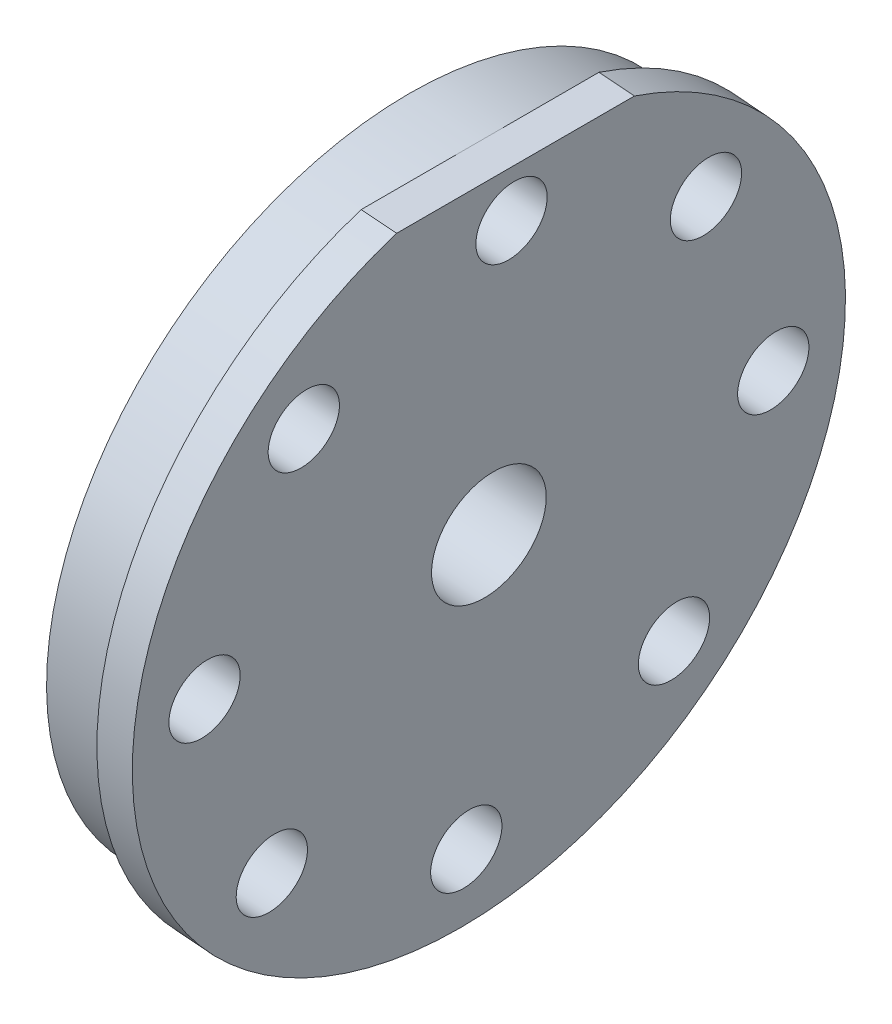
SolidWorks part; units mm, degrees
ref_plane "Front Plane" through (0, 0, 0) normal (0, 0, 1) x (1, 0, 0)
ref_plane "Top Plane" through (0, 0, 0) normal (0, 1, 0) x (1, 0, 0)
ref_plane "Right Plane" through (0, 0, 0) normal (1, 0, 0) x (0, 0, -1)
sketch "Sketch1" plane through (234.2789, -18.689, 0) normal (0.9968, -0.0795, 0) x (0, 0, -1)
  circle A1 centre (-43.1743, 8.5503) radius 14.9606
  dimension "D1" = 29.9212
extrude "Boss-Extrude1" add sketch "Sketch1" against normal blind 4.7625
sketch "Sketch2" plane through (234.2789, -18.689, 0) normal (0.9968, -0.0795, 0) x (0, 0, -1)
  circle A0 centre (-43.1743, 8.5503) radius 2.5527
  dimension "D1" = 5.1054
extrude "Cut-Extrude1" cut sketch "Sketch2" against normal blind 6.35
sketch "Sketch3" plane through (229.5315, -18.3103, 0) normal (-0.9968, 0.0795, 0) x (0, 0, 1)
  circle A0 centre (43.1743, 21.2503) radius 1.5875
  circle A1 centre (43.1743, 8.5503) radius 14.9606 construction
  circle A2 centre (43.1743, 8.5503) radius 14.9606
  circle A3 centre (52.1545, 17.5306) radius 1.5875
  circle A4 centre (55.8743, 8.5503) radius 1.5875
  circle A5 centre (52.1545, -0.4299) radius 1.5875
  circle A6 centre (43.1743, -4.1497) radius 1.5875
  circle A7 centre (34.194, -0.4299) radius 1.5875
  circle A8 centre (30.4743, 8.5503) radius 1.5875
  circle A9 centre (34.194, 17.5306) radius 1.5875
  point P21 (43.1743, 8.5503)
  dimension "D1" = 3.175
  dimension "D3" = 12.7
  dimension "D2" = 8
extrude "Cut-Extrude2" cut sketch "Sketch3" against normal blind 10 contours A8 | A0 | A3 | A4 | A5 | A6 | A7 | A9 region at (231.2213, 2.8727, 43.1743) region at (230.9255, -0.8352, 52.1545) region at (230.2114, -9.787, 55.8743) region at (229.4973, -18.7389, 52.1545) region at (229.2015, -22.4468, 43.1743) region at (229.4973, -18.7389, 34.194) region at (230.2114, -9.787, 30.4743)
sketch "Sketch4" plane through (234.2789, -18.689, 0) normal (0.9968, -0.0795, 0) x (0, 0, -1)
  line L0 (-58.1349, 8.5503) -> (-28.2137, 8.5503) construction
  circle A0 centre (-43.1743, 8.5503) radius 14.9606 construction
sketch "Sketch5" plane through (234.2789, -18.689, 0) normal (-0.9968, 0.0795, 0) x (0, 0, 1)
  circle A0 centre (43.1743, 8.5503) radius 14.9606 construction
  circle A1 centre (43.1743, 8.5503) radius 14.9606
  circle A2 centre (43.1743, 8.5503) radius 15.875
  dimension "D1" = 31.75
extrude "Boss-Extrude2" add sketch "Sketch5" along normal blind 1.5875
ref_axis "Axis1" through (230.2414, -9.7894, 43.1743) along (0.9968, -0.0795, 0)
ref_point "Point1"
sketch "Sketch6" plane through (234.2789, -18.689, 0) normal (0.9968, -0.0795, 0) x (0, 0, -1)
  line L0 (-48.4843, 23.5109) -> (-37.8643, 23.5109)
  circle A0 centre (-43.1743, 8.5503) radius 15.875 construction
  circle A1 centre (-43.1743, 8.5503) radius 14.9606 construction
  circle A2 centre (-43.1743, 8.5503) radius 15.875
  circle A3 centre (-43.1743, 8.5503) radius 15.875
  circle M15 centre (-43.1743, 8.5503) radius 15.875
  dimension "D1" = 0
extrude "Cut-Extrude3" cut sketch "Sketch6" against normal blind 2.54 contours L0 M15 region at (236.1776, 5.113, 43.1743)
